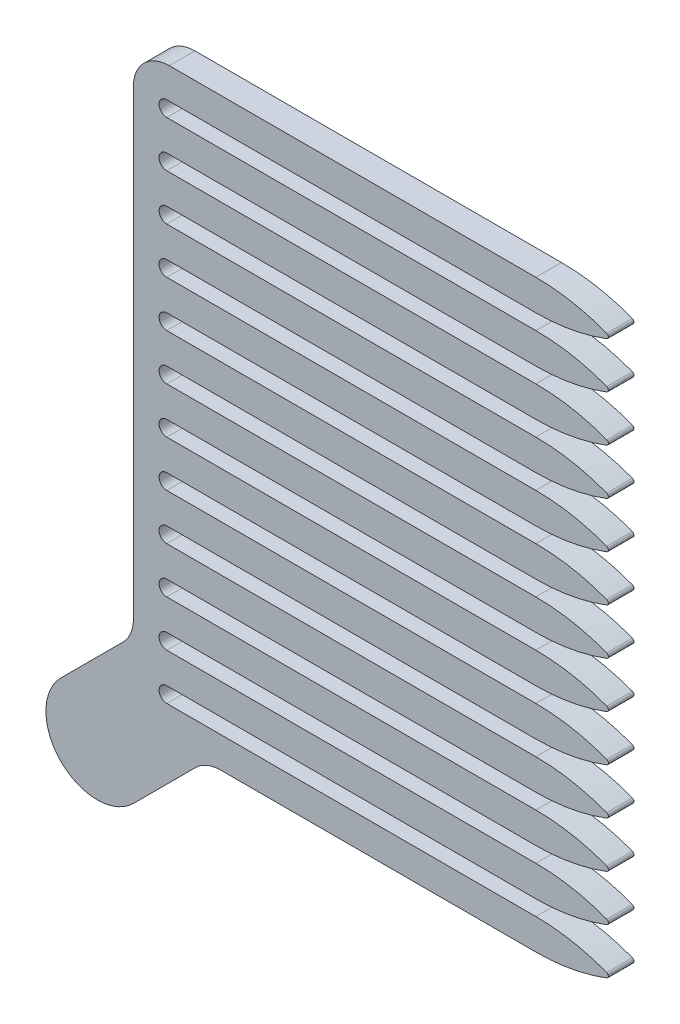
SolidWorks part; units mm, degrees
ref_plane "Ebene vorne" through (0, 0, 0) normal (0, 0, 1) x (1, 0, 0)
ref_plane "Ebene oben" through (0, 0, 0) normal (0, 1, 0) x (1, 0, 0)
ref_plane "Ebene rechts" through (0, 0, 0) normal (1, 0, 0) x (0, 0, -1)
sketch "Skizze1" plane through (0, 0, 0) normal (0, 0, 1) x (1, 0, 0)
  line L0 (0, 0) -> (0, 3) construction
  line L1 (0, 3) -> (-78.5, 3)
  line L2 (-78.5, 3) -> (-78.5, -1.9334)
  line L3 (-72, -3) -> (0, -3)
  line L4 (0, -3) -> (0, 0) construction
  line L5 (0, 0) -> (15, 0) construction
  line L7 (-78.5, -1.9334) -> (-78.5, -6)
  line L8 (-78.5, -6) -> (-72, -6)
  line L9 (-72, -3) -> (-72, -6)
  arc A0 (0, -3) -> (15, 0) centre (0, 36) ccw
  arc A1 (0, 3) -> (15, 0) centre (0, -36) cw
  dimension "D5" = 15
  dimension "D1" = 9
  dimension "D2" = 3
  dimension "D3" = 6.5
  dimension "D4" = 72
extrude "Aufsatz-Linear austragen1" add sketch "Skizze1" along normal blind 5
sketch "Skizze2" plane through (0, 0, 5) normal (0, 0, 1) x (1, 0, 0)
  line L0 (-72, -6) -> (-72, -3) construction
  circle A0 centre (-72, -4.5) radius 1.5
extrude "Schnitt-Linear austragen1" cut sketch "Skizze2" against normal through all
fillet "Verrundung2" radius 0.5 1 edges at (15, 0, 2.5)
pattern_linear "Lineares Muster1" count 13 spacing 9 along (0, -1, 0) of bodies 110 101
combine bodies "Kombinieren1" operation type add bodies to combine 110 102 103 104 105 106 107 108 113 114 115 116 117
sketch "Skizze3" plane through (0, 0, 5) normal (0, 0, 1) x (1, 0, 0)
  line L7 (-72, -111) -> (0, -111) construction
  line L8 (-78.5, -114) -> (-71.1381, -114)
  line L9 (-78.5, -114) -> (-78.5, -111)
  line L10 (-78.5, -111) -> (-71.1381, -111)
  line L11 (-71.1381, -114) -> (-71.1381, -111)
extrude "Schnitt-Linear austragen2" cut sketch "Skizze3" against normal through all
sketch "Skizze5" [suppressed] plane through (0, 0, 5) normal (0, 0, 1) x (1, 0, 0)
  line L1 (-114.5, -111) -> (14.1473, -111)
  line L2 (-114.5, -111) -> (-114.5, -75)
  line L3 (-114.5, -75) -> (14.1473, -75)
  line L4 (14.1473, -111) -> (14.1473, -75)
  line L5 (-114.5, 3) -> (-114.5, -111) construction
  arc A1 (13.8246, -108.4675) -> (13.8246, -107.5325) centre (13.6473, -108) ccw construction
extrude "Schnitt-Linear austragen3" [suppressed] cut sketch "Skizze5" against normal through all contours L4 L3 L2 L1
sketch "Skizze4" plane through (0, 0, 5) normal (0, 0, 1) x (1, 0, 0)
  line L0 (-64.3579, -111) -> (-78.5, -111)
  line L5 (-78.5, -96.8579) -> (-92.6421, -111)
  line L10 (-78.5, 3) -> (-78.5, -111) construction
  line L11 (-92.6421, -111) -> (-78.5, -125.1421) construction
  line L12 (-78.5, -125.1421) -> (-64.3579, -111)
  line L15 (-78.5, -111) -> (-78.5, -96.8579)
  line L17 (-78.5, -111) -> (0, -111) construction
  arc A0 (-92.6421, -111) -> (-78.5, -125.1421) centre (-85.5711, -118.0711) ccw
  dimension "D1" = 20
  dimension "D2" = 135
  dimension "D3" = 20
extrude "Aufsatz-Linear austragen2" add sketch "Skizze4" against normal up to surface (5 mm away) up to face at (-19.6971, -54, 0)
fillet "Verrundung1" radius 7 3 edges at (-78.5, 3, 2.5) (-78.5, -96.8579, 2.5) (-64.3579, -111, 2.5)
sketch "Skizze6" [suppressed] plane through (0, 0, 5) normal (0, 0, 1) x (1, 0, 0)
  line L1 (-114.5, 3) -> (-114.5, -75) construction
  line L3 (-114.5, -11.1421) -> (-128.6421, 3)
  line L5 (-114.5, 17.1421) -> (-100.3579, 3)
  line L8 (0, 3) -> (-114.5, 3) construction
  line L9 (-114.5, -11.1421) -> (-114.5, 3)
  line L10 (-114.5, 3) -> (-100.3579, 3)
  line L11 (-128.6421, 3) -> (-114.5, 17.1421) construction
  arc A1 (-128.6421, 3) -> (-114.5, 17.1421) centre (-121.5711, 10.0711) cw
  point P12 (-121.5711, 10.0711)
  dimension "D1" = 20
  dimension "D2" = 20
  dimension "D3" = 135
extrude "Aufsatz-Linear austragen3" [suppressed] add sketch "Skizze6" against normal up to surface (5 mm away) up to face at (-23.7579, -56.707, 0)
fillet "Verrundung3" [suppressed] radius 7
